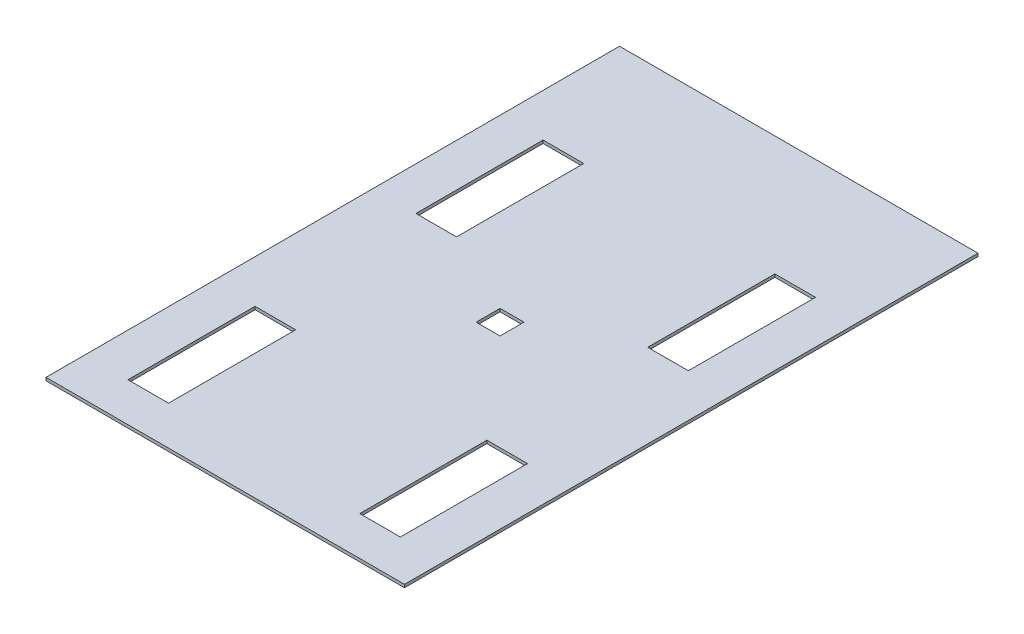
SolidWorks part; units mm, degrees
ref_plane "Front Plane" through (0, 0, 0) normal (0, 0, 1) x (1, 0, 0)
ref_plane "Top Plane" through (0, 0, 0) normal (0, 1, 0) x (1, 0, 0)
ref_plane "Right Plane" through (0, 0, 0) normal (1, 0, 0) x (0, 0, -1)
sketch "Sketch1" plane through (0, 0, 0) normal (0, 1, 0) x (1, 0, 0)
  line L1 (-190.5, -304.8) -> (190.5, -304.8)
  line L2 (-190.5, -304.8) -> (-190.5, 304.8)
  line L3 (-190.5, 304.8) -> (190.5, 304.8)
  line L4 (190.5, -304.8) -> (190.5, 304.8)
  line L5 (0, 304.8) -> (0, -304.8) construction
  line L6 (-190.5, 0) -> (190.5, 0) construction
  point P0 (0, 0)
  dimension "D1" = 381
  dimension "D2" = 609.6
extrude "Boss-Extrude1" add sketch "Sketch1" along normal blind 3.175
sketch "Sketch2" plane through (0, 3.175, 0) normal (0, 1, 0) x (1, 0, 0)
  line L0 (0, -1000) -> (0, 49000) construction
  line L5 (190.5, 304.8) -> (-190.5, 304.8) construction
  line L6 (101.6, -263.4234) -> (144.78, -263.4234)
  line L7 (101.6, 42.672) -> (144.78, 42.672)
  line L8 (101.6, 42.672) -> (101.6, 177.8)
  line L9 (101.6, 177.8) -> (144.78, 177.8)
  line L10 (144.78, 42.672) -> (144.78, 177.8)
  line L11 (123.19, 177.8) -> (123.19, 42.672) construction
  line L12 (101.6, 110.236) -> (144.78, 110.236) construction
  line L17 (101.6, -263.4234) -> (101.6, -128.2954)
  line L18 (101.6, -128.2954) -> (144.78, -128.2954)
  line L23 (144.78, -263.4234) -> (144.78, -128.2954)
  line L24 (123.19, -128.2954) -> (123.19, -263.4234) construction
  line L25 (101.6, -195.8594) -> (144.78, -195.8594) construction
  line L26 (-123.19, -128.2954) -> (-123.19, -263.4234) construction
  line L27 (-144.78, -263.4234) -> (-144.78, -128.2954)
  line L28 (-101.6, -263.4234) -> (-101.6, -128.2954)
  line L29 (-101.6, -263.4234) -> (-144.78, -263.4234)
  line L30 (-101.6, -195.8594) -> (-144.78, -195.8594) construction
  line L31 (-101.6, -128.2954) -> (-144.78, -128.2954)
  line L32 (-101.6, 110.236) -> (-144.78, 110.236) construction
  line L33 (-123.19, 177.8) -> (-123.19, 42.672) construction
  line L34 (-144.78, 42.672) -> (-144.78, 177.8)
  line L35 (-101.6, 177.8) -> (-144.78, 177.8)
  line L36 (-101.6, 42.672) -> (-101.6, 177.8)
  line L37 (-101.6, 42.672) -> (-144.78, 42.672)
  point P1 (123.19, -195.8594)
  point P4 (123.19, 110.236)
  point P20 (-123.19, -195.8594)
  point P29 (-123.19, 110.236)
  dimension "D1" = 135.128
  dimension "D2" = 43.18
  dimension "D3" = 135.128
  dimension "D4" = 306.0954
  dimension "D5" = 127
  dimension "D6" = 123.19
extrude "Cut-Extrude1" cut sketch "Sketch2" against normal through all
sketch "Sketch4" plane through (0, 0, 0) normal (0, 1, 0) x (1, 0, 0)
  line L5 (144.78, 177.8) -> (101.6, 177.8) construction
  line L6 (-12.7, -25.4) -> (12.7, -25.4)
  line L7 (-12.7, -25.4) -> (-12.7, 0)
  line L8 (-12.7, 0) -> (12.7, 0)
  line L9 (12.7, -25.4) -> (12.7, 0)
  line L10 (0, 0) -> (0, -25.4) construction
  line L11 (-12.7, -12.7) -> (12.7, -12.7) construction
  point P0 (0, -12.7)
  dimension "D1" = 25.4
  dimension "D2" = 177.8
  dimension "D3" = 25.4
extrude "Cut-Extrude3" cut sketch "Sketch4" along normal through all
